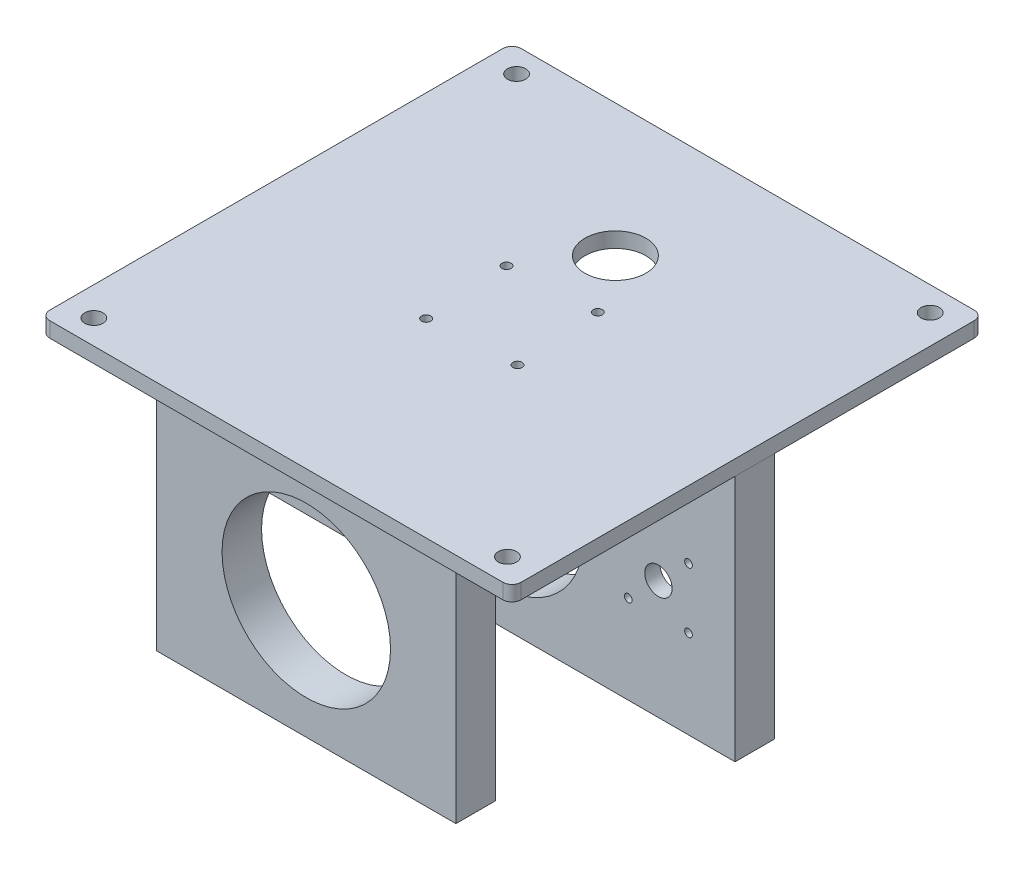
SolidWorks part; units mm, degrees
ref_plane "Front Plane" through (0, 0, 0) normal (0, 0, 1) x (1, 0, 0)
ref_plane "Top Plane" through (0, 0, 0) normal (0, 1, 0) x (1, 0, 0)
ref_plane "Right Plane" through (0, 0, 0) normal (1, 0, 0) x (0, 0, -1)
sketch "Sketch1" plane through (0, 0, 0) normal (0, 1, 0) x (1, 0, 0)
  line L0 (74.6537, 78.4791) -> (-74.3463, 78.4791)
  line L1 (-77.3463, 75.4791) -> (-77.3463, -73.5209)
  line L2 (-74.3463, -76.5209) -> (74.6537, -76.5209)
  line L3 (77.6537, -73.5209) -> (77.6537, 75.4791)
  circle A0 centre (0.1537, 34.9791) radius 10
  arc A1 (77.6537, 75.4791) -> (74.6537, 78.4791) centre (74.6537, 75.4791) ccw
  arc A2 (-74.3463, 78.4791) -> (-77.3463, 75.4791) centre (-74.3463, 75.4791) ccw
  arc A3 (-77.3463, -73.5209) -> (-74.3463, -76.5209) centre (-74.3463, -73.5209) ccw
  arc A4 (74.6537, -76.5209) -> (77.6537, -73.5209) centre (74.6537, -73.5209) ccw
  circle A5 centre (68.1537, -68.5209) radius 3
  circle A6 centre (68.1537, 70.4791) radius 3
  circle A7 centre (-67.8463, 70.4791) radius 3
  circle A8 centre (-67.8463, -68.5209) radius 3
  circle A9 centre (-14.8624, 14.1897) radius 1.5
  circle A10 centre (-13.0568, -14.0369) radius 1.5
  circle A11 centre (15.1698, -12.2314) radius 1.5
  circle A12 centre (13.3642, 15.9952) radius 1.5
extrude "Boss-Extrude1" add sketch "Sketch1" against normal blind 5
ref_plane "Plane1" through (0, 0, 66.5209) normal (0, 0, 1) x (1, 0, 0)
sketch "Sketch2" plane through (0, 0, 66.5209) normal (0, 0, 1) x (1, 0, 0)
  line L1 (-49.2157, -5) -> (-49.2157, -86.4627)
  line L2 (-49.2157, -86.4627) -> (49.2157, -86.4627)
  line L3 (49.2157, -86.4627) -> (49.2157, -5)
  line L4 (49.2157, -5) -> (-49.2157, -5)
  line L5 (-74.3463, -5) -> (74.6537, -5) construction
  circle A0 centre (0, -47.5) radius 27.7
  point P0 (0, -5)
  dimension "D1" = 42.5
  dimension "D2" = 98.4315
  dimension "D3" = 81.4627
  dimension "D4" = 49.2157
extrude "Boss-Extrude2" add sketch "Sketch2" against normal blind 13
ref_plane "Plane2" through (0, 0, 3.0209) normal (0, 0, -1) x (-1, 0, 0)
sketch "Sketch3" plane through (0, 0, 3.0209) normal (0, 0, -1) x (-1, 0, 0)
  line L0 (-77.5, -5) -> (-77.5, -86.4627)
  line L1 (-77.5, -86.4627) -> (77.5, -86.4627)
  line L2 (77.5, -86.4627) -> (77.5, -5)
  line L3 (77.5, -5) -> (-77.5, -5)
  circle A0 centre (0, -47.5) radius 27.7
  circle A1 centre (42.4005, -57.3995) radius 1.2645
  circle A2 centre (42.4005, -37.6005) radius 1.2645
  circle A3 centre (52.3, -47.5) radius 4.5
  circle A4 centre (62.1995, -37.6005) radius 1.2645
  circle A5 centre (62.1995, -57.3995) radius 1.2645
  circle A6 centre (-42.4005, -57.391) radius 1.2645
  circle A7 centre (-42.4005, -37.592) radius 1.2645
  circle A8 centre (-52.3, -47.5) radius 4.5
  circle A9 centre (-62.1995, -57.391) radius 1.2645
  circle A10 centre (-62.1995, -37.592) radius 1.2645
  point P30 (0, -5)
  dimension "D1" = 55.4
  dimension "D2" = 52.3
  dimension "D3" = 38.9627
  dimension "D4" = 81.4627
  dimension "D5" = 155
  dimension "D6" = 9.8995
  dimension "D7" = 9.8995
  dimension "D8" = 9.8995
  dimension "D9" = 9.8995
  dimension "D10" = 9.8995
  dimension "D11" = 9.8995
  dimension "D12" = 9.8995
  dimension "D13" = 9.8995
  dimension "D14" = 25.2
  dimension "D15" = 25.2
  dimension "D16" = 38.9627
  dimension "D17" = 9.8995
  dimension "D18" = 9.908
  dimension "D19" = 9.891
  dimension "D20" = 9.8995
  dimension "D21" = 9.8995
  dimension "D22" = 9.891
  dimension "D23" = 9.908
  dimension "D24" = 9.8995
  dimension "D25" = 90
  dimension "D26" = 5
extrude "Boss-Extrude3" add sketch "Sketch3" along normal blind 13
sketch "Sketch4" plane through (0, 0, -9.9791) normal (0, 0, -1) x (-1, 0, 0)
  circle A0 centre (52.3, -47.5) radius 11
  circle A1 centre (52.3, -47.5) radius 18.5
  circle M4 centre (62.1995, -57.3995) radius 1.2645
  circle M5 centre (52.3, -47.5) radius 4.5
  circle M6 centre (42.4005, -57.3995) radius 1.2645
  circle M13 centre (42.4005, -37.6005) radius 1.2645
  circle M14 centre (62.1995, -37.6005) radius 1.2645
  dimension "D1" = 37
  dimension "D2" = 22
extrude "Cut-Extrude1" cut sketch "Sketch4" against normal blind 5 contours A1 A0 M4 M6 M14 M13 | A0 M5 region at (-41.6111, -47.5, -9.9791) region at (-34.3233, -47.5, -9.9791)
extrude "Cut-Extrude2" cut sketch "Sketch4<3>" against normal blind 8 contours A0 M5 region at (-41.6111, -47.5, -9.9791)
sketch "Sketch4<3>" plane through (0, 0, -9.9791) normal (0, 0, -1) x (-1, 0, 0) same geometry as "Sketch4"
pattern_linear "LPattern1" count 2 spacing 104.6 along (1, 0, 0) of "Cut-Extrude1", "Cut-Extrude2"
sketch "Sketch5" plane through (0, 0, 0) normal (0, 1, 0) x (1, 0, 0)
  line L0 (70.8, 9.9791) -> (33.8, 9.9791) construction
  line L1 (40.4925, 9.9791) -> (64.0907, 9.9791)
  line L2 (40.4925, 9.9791) -> (40.4925, 4.9791)
  line L3 (40.4925, 4.9791) -> (64.0907, 4.9791)
  line L4 (64.0907, 9.9791) -> (64.0907, 4.9791)
  line L5 (70.8, 4.9791) -> (33.8, 4.9791) construction
extrude "Cut-Extrude3" cut sketch "Sketch5" against normal blind 23 from offset 36 offset against normal yes
